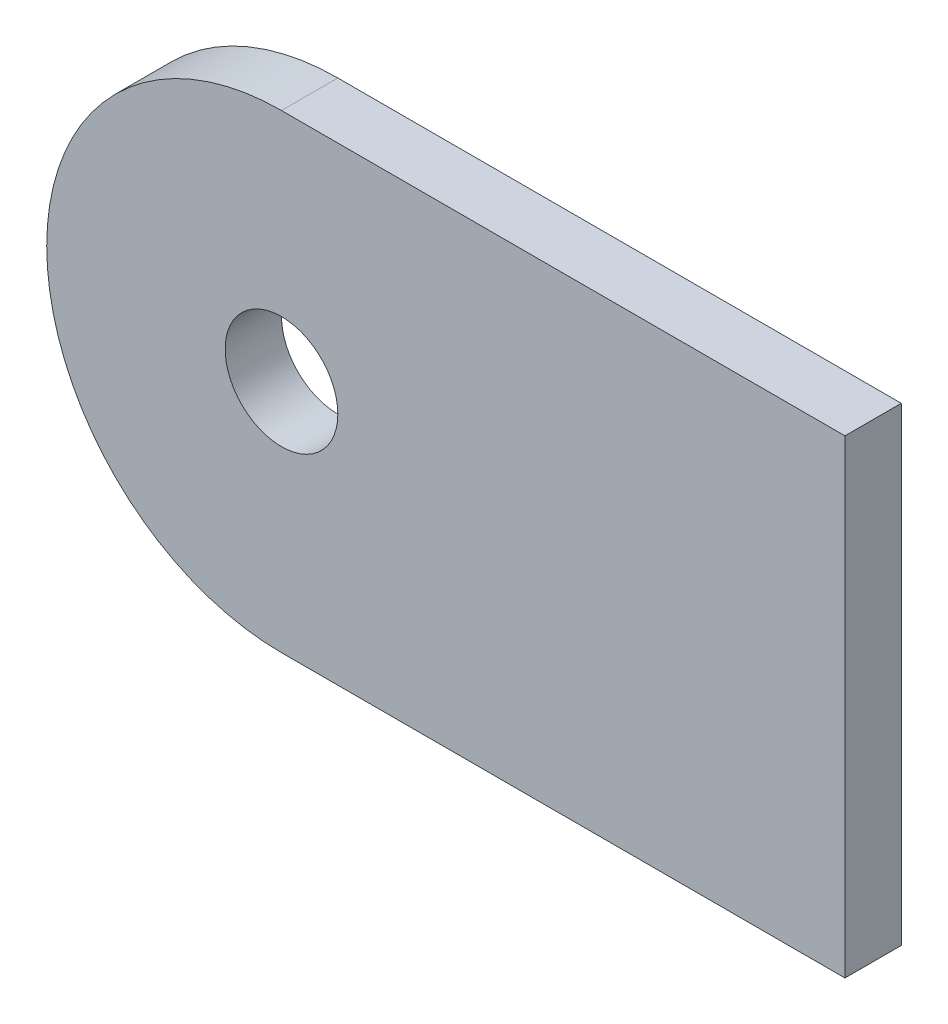
SolidWorks part; units mm, degrees
ref_plane "Front Plane" through (0, 0, 0) normal (0, 0, 1) x (1, 0, 0)
ref_plane "Top Plane" through (0, 0, 0) normal (0, 1, 0) x (1, 0, 0)
ref_plane "Right Plane" through (0, 0, 0) normal (1, 0, 0) x (0, 0, -1)
sketch "Sketch1" plane through (0, 0, 25.798) normal (0, 0, 1) x (1, 0, 0)
  line L1 (-1.6088, 3.0507) -> (-31.6088, 3.0507)
  line L2 (-1.6088, 3.0507) -> (-1.6088, 28.0507)
  line L3 (-1.6088, 28.0507) -> (-31.6088, 28.0507)
  arc A0 (-31.6088, 3.0507) -> (-31.6088, 28.0507) centre (-31.6088, 15.5507) cw
  circle A1 centre (-31.6088, 15.5507) radius 3
  dimension "D1" = 25
  dimension "D2" = 30
extrude "Boss-Extrude1" add sketch "Sketch1" along normal blind 3
